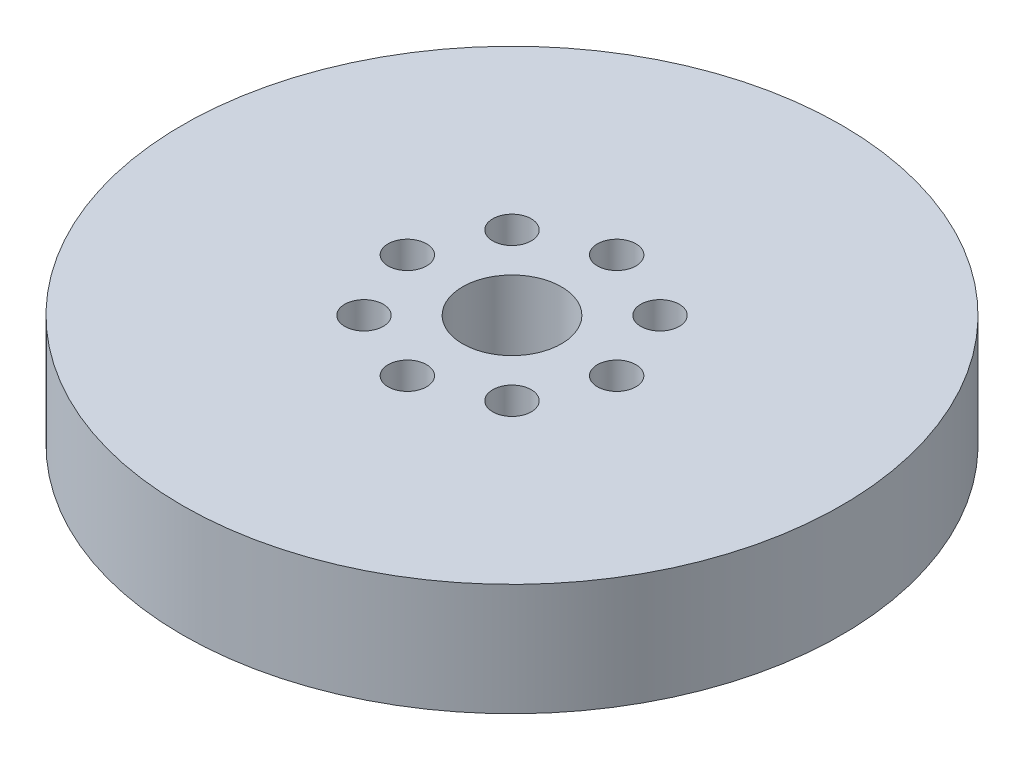
SolidWorks part; units mm, degrees
ref_plane "Front Plane" through (0, 0, 0) normal (0, 0, 1) x (1, 0, 0)
ref_plane "Top Plane" through (0, 0, 0) normal (0, 1, 0) x (1, 0, 0)
ref_plane "Right Plane" through (0, 0, 0) normal (1, 0, 0) x (0, 0, -1)
sketch "Sketch1" plane through (0, 0, 0) normal (0, 1, 0) x (1, 0, 0)
  circle A0 centre (0, 0) radius 50
  dimension "FLANGE_OD" = 100
extrude "Boss-Extrude1" add sketch "Sketch1" along normal blind 17
sketch "Sketch2" plane through (0, 0, 0) normal (0, 1, 0) x (1, 0, 0)
  circle A0 centre (0, 0) radius 7.5
  dimension "BORE_D" = 15
extrude "Cut-Extrude1" cut sketch "Sketch2" along normal through all
sketch "Sketch3" plane through (0, 17, 0) normal (0, 1, 0) x (1, 0, 0)
  circle A0 centre (0, 0) radius 15.88 construction
  circle A1 centre (-15.88, 0) radius 2.9202
  dimension "BOLT_D" = 5.8404
  dimension "BOLT_PCD" = 31.7599
extrude "Cut-Extrude2" cut sketch "Sketch3" against normal blind 10.7748
pattern_circular "CirPattern1" count 8 over 360 about axis through (0, 0, 0) along (0, 1, 0) of "Cut-Extrude2"
